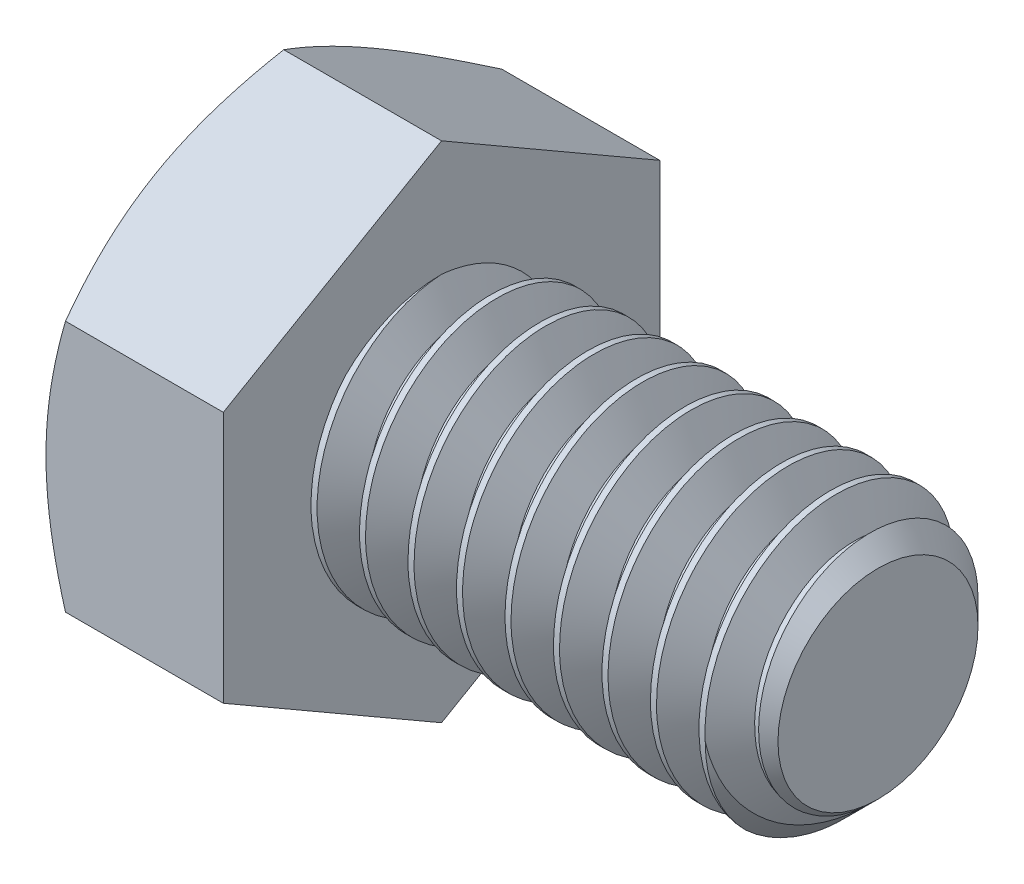
SolidWorks part; units mm, degrees
material "AISI 304"
ref_plane "Front Plane" through (0, 0, 0) normal (0, 0, 1) x (1, 0, 0)
ref_plane "Top Plane" through (0, 0, 0) normal (0, 1, 0) x (1, 0, 0)
ref_plane "Right Plane" through (0, 0, 0) normal (1, 0, 0) x (0, 0, -1)
sketch "Sketch1" plane through (0, 0, 0) normal (0, 0, 1) x (1, 0, 0)
  line L0 (-8.9297, 0) -> (8.9297, 0) construction
  line L1 (8.9297, 3.9688) -> (8.9297, -3.9688) construction
  line L2 (-3.7703, 6.35) -> (-3.7703, -6.35) construction
  line L3 (-8.9297, 6.35) -> (-8.9297, -6.35) construction
  point P9 (-3.7703, 0)
  point P10 (3.9908, -3.9688)
  dimension "D1" = 4.9389
  dimension "Screw Dia" = 7.9375
  dimension "Hex" = 12.7
  dimension "Head Ht" = 5.1594
  dimension "Screw Lenght" = 12.7
ref_plane "Plane2" through (8.9297, 0, 0) normal (1, 0, 0) x (0, 0, -1)
sketch "Sketch5" plane through (8.9297, 0, 0) normal (1, 0, 0) x (0, 0, -1)
  circle A0 centre (0, 0) radius 3.9688
extrude "Boss-Extrude3" add sketch "Sketch5" against normal up to vertex (12.7 mm away) up to point (-3.7703, 0, 0)
sketch "Sketch9" plane through (8.9297, 0, 0) normal (1, 0, 0) x (0, 0, -1)
  circle A1 centre (0, 0) radius 3.9688
  circle A2 centre (0, 0) radius 3.9688
  dimension "D1" = 0
curve "Helix/Spiral1" pitch 1.4111 height 14.1111 turns 10 parameters "Pitch"=1.4111
chamfer "Chamfer1" distance 1.0583 angle 45 1 edges at (8.9297, 0, -3.9688)
sketch "Sketch10" plane through (0, 0, 0) normal (0, 0, 1) x (1, 0, 0)
  line L0 (8.9297, 3.9688) -> (9.4589, 3.0522)
  line L1 (9.4589, 3.0522) -> (9.6352, 3.0522)
  line L2 (9.6352, 3.0522) -> (10.1644, 3.9688)
  line L3 (8.9297, 3.9688) -> (10.1644, 3.9688)
  line L4 (9.547, 3.9688) -> (9.547, 3.0522) construction
  line L5 (9.1943, 3.5105) -> (9.8998, 3.5105) construction
  dimension "D1" = 60
  dimension "D2" = 0.1764
  dimension "D3" = 0.7056
sweep "Cut-Sweep1" cut profiles "Sketch10" path "Helix/Spiral1"
sketch "Sketch6" plane through (-3.7703, 0, 0) normal (-1, 0, 0) x (0, 0, 1)
  line L0 (0, 6.35) -> (0, -6.35) construction
  line L1 (6.35, 3.6662) -> (0, 7.3323)
  line L2 (0, 7.3323) -> (-6.35, 3.6662)
  line L3 (-6.35, 3.6662) -> (-6.35, -3.6662)
  line L4 (-6.35, -3.6662) -> (0, -7.3323)
  line L5 (0, -7.3323) -> (6.35, -3.6662)
  line L6 (6.35, -3.6662) -> (6.35, 3.6662)
  circle A0 centre (0, 0) radius 6.35 construction
extrude "Boss-Extrude4" add sketch "Sketch6" along normal up to vertex (5.1594 mm away) up to point (-8.9297, -6.35, 0)
sketch "Sketch7" plane through (-8.9297, 0, 0) normal (-1, 0, 0) x (0, 0, 1)
  circle A0 centre (0, 0) radius 6.35 construction
  circle A1 centre (0, 0) radius 6.35
sketch "Sketch8" plane through (-8.9297, 0, 0) normal (-1, 0, 0) x (0, 0, 1)
  circle A0 centre (0, 0) radius 6.35 construction
  circle A1 centre (0, 0) radius 6.35
extrude "Cut-Extrude3" cut sketch "Sketch8" against normal through all draft 60 flip side to cut
equation "\"D2@Sketch10\" = \"Pitch@Helix/Spiral1\"*.125"
equation "\"D3@Sketch10\" = \"Pitch@Helix/Spiral1\"*.5"
equation "\"D3@Helix/Spiral1\" = \"Screw Lenght@Sketch1\"+\"Pitch@Helix/Spiral1\""
equation "\"D1@Chamfer1\" = \"Pitch@Helix/Spiral1\"*.75"
equation "\"D1@Sketch1\" = \"Pitch@Helix/Spiral1\"*3.5"
